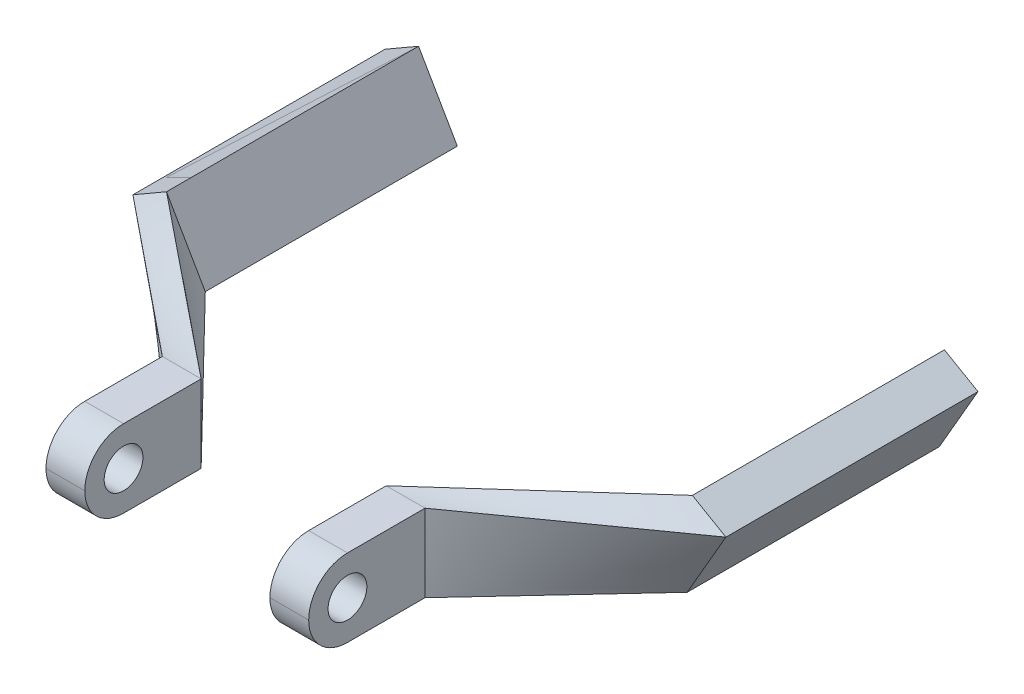
SolidWorks part; units mm, degrees
ref_plane "Front Plane" through (0, 0, 0) normal (0, 0, 1) x (1, 0, 0)
ref_plane "Top Plane" through (0, 0, 0) normal (0, 1, 0) x (1, 0, 0)
ref_plane "Right Plane" through (0, 0, 0) normal (1, 0, 0) x (0, 0, -1)
sketch "Sketch1" plane through (0, 0, 0) normal (0, 0, 1) x (1, 0, 0)
  line L0 (0, 0) -> (0, 68.1848) construction
  line L1 (66.4573, -65.1073) -> (57.797, -60.1073)
  line L2 (46.25, -80.1073) -> (92.5, 0)
  line L3 (92.5, 0) -> (46.25, 80.1073)
  line L4 (46.25, 80.1073) -> (-46.25, 80.1073)
  line L5 (-46.25, 80.1073) -> (-92.5, 0)
  line L6 (-92.5, 0) -> (-46.25, -80.1073)
  line L7 (-46.25, -80.1073) -> (46.25, -80.1073)
  line L8 (66.4573, -65.1073) -> (76.4573, -47.7868)
  line L9 (76.4573, -47.7868) -> (67.797, -42.7868)
  line L10 (-76.4573, -47.7868) -> (-67.797, -42.7868)
  line L11 (-66.4573, -65.1073) -> (-76.4573, -47.7868)
  line L12 (-66.4573, -65.1073) -> (-57.797, -60.1073)
  circle A0 centre (0, 0) radius 80.1073 construction
  dimension "D1" = 185
  dimension "D2" = 20
  dimension "D3" = 20
  dimension "D4" = 10
extrude "Boss-Extrude1" add sketch "Sketch1" along normal blind 50 and the other way blind 15 contours L11 L12 L6 L10 | L8 L9 L2 L1 region at (67.1271, -53.9471, 0) region at (-67.1271, -53.9471, 0)
sketch "Sketch2" plane through (0, 0, 50) normal (0, 0, 1) x (1, 0, 0)
  line L0 (76.4573, -47.7868) -> (67.797, -42.7868) construction
  line L1 (23.868, -45.1073) -> (33.868, -45.1073)
  line L2 (23.868, -45.1073) -> (23.868, -65.1073)
  line L3 (23.868, -65.1073) -> (33.868, -65.1073)
  line L4 (33.868, -45.1073) -> (33.868, -65.1073)
  line L5 (57.797, -60.1073) -> (67.797, -42.7868) construction
extrude "Boss-Extrude2" add sketch "Sketch2" along normal blind 30 from offset 35 separate body
loft "Loft2" add section face at (67.1271, -53.9471, 50) section face at (28.868, -55.1073, 85) connector at (66.4573, -65.1073, 50) connector at (33.868, -65.1073, 85)
ref_plane "Plane1" through (0, 0, 0) normal (-1, 0, 0) x (0, 0, 1)
mirror "Mirror3" about plane through (0, 0, 0) normal (-1, 0, 0) of bodies 105
sketch "Sketch3" plane through (-33.868, 0, 0) normal (-1, 0, 0) x (0, 0, 1)
  line L0 (115, -65.1073) -> (115, -45.1073) construction
  circle A0 centre (105, -55.1073) radius 10
  circle A1 centre (105, -55.1073) radius 5
  point P3 (157.3981, -39.0617)
  point P6 (115, -55.1073)
  dimension "D1" = 20
  dimension "D2" = 10
  dimension "D3" = 10
extrude "Cut-Extrude1" cut sketch "Sketch3" against normal through all contours A1 region at (-33.868, -55.1073, 105)
sketch "Sketch4" [suppressed] plane through (-33.868, 0, 0) normal (-1, 0, 0) x (0, 0, 1)
  line L2 (170, -42.9423) -> (90, -42.9423) construction
  line L4 (165.707, -44.7307) -> (170, -42.9423)
  line L5 (170, -42.9423) -> (160, -42.9423)
  arc A0 (165.707, -44.7307) -> (160, -42.9423) centre (160, -52.9423) ccw
  dimension "D1" = 20
extrude "Cut-Extrude5" [suppressed] cut sketch "Sketch4" against normal through all
fillet "Fillet1" [suppressed] radius 10
fillet "Fillet2" [suppressed] radius 10
fillet "Fillet3" radius 10 2 edges at (-28.868, -65.1073, 115) (-28.868, -45.1073, 115)
fillet "Fillet4" radius 10 2 edges at (28.868, -45.1073, 115) (28.868, -65.1073, 115)
sketch "Sketch5" plane through (33.868, 0, 0) normal (1, 0, 0) x (0, 0, -1)
  circle A0 centre (-112, -48.1073) radius 1.5
  circle A2 centre (-64.3265, 55.1517) radius 1.5
  circle A3 centre (42.3989, 94.4566) radius 1.5
  circle A4 centre (145.6579, 46.7831) radius 1.5
  circle A5 centre (184.9629, -59.9423) radius 1.5
  circle A6 centre (137.2894, -163.2013) radius 1.5
  circle A7 centre (30.564, -202.5062) radius 1.5
  circle A8 centre (-72.6951, -154.8328) radius 1.5
  circle A9 centre (-105, -45.2079) radius 1.5
  circle A10 centre (-98, -48.1073) radius 1.5
  circle A11 centre (-95.1005, -55.1073) radius 1.5
  circle A12 centre (-98, -62.1073) radius 1.5
  circle A13 centre (-105, -65.0068) radius 1.5
  circle A14 centre (-112, -62.1073) radius 1.5
  circle A15 centre (-114.8995, -55.1073) radius 1.5
  circle A17 centre (-105, -55.1073) radius 5 construction
  point P5 (0, 0)
  point P22 (36.4814, -54.0248)
  point P37 (-105, -55.1073)
  dimension "D2" = 3
  dimension "D1" = 7
  dimension "D3" = 8
  dimension "D4" = 8
